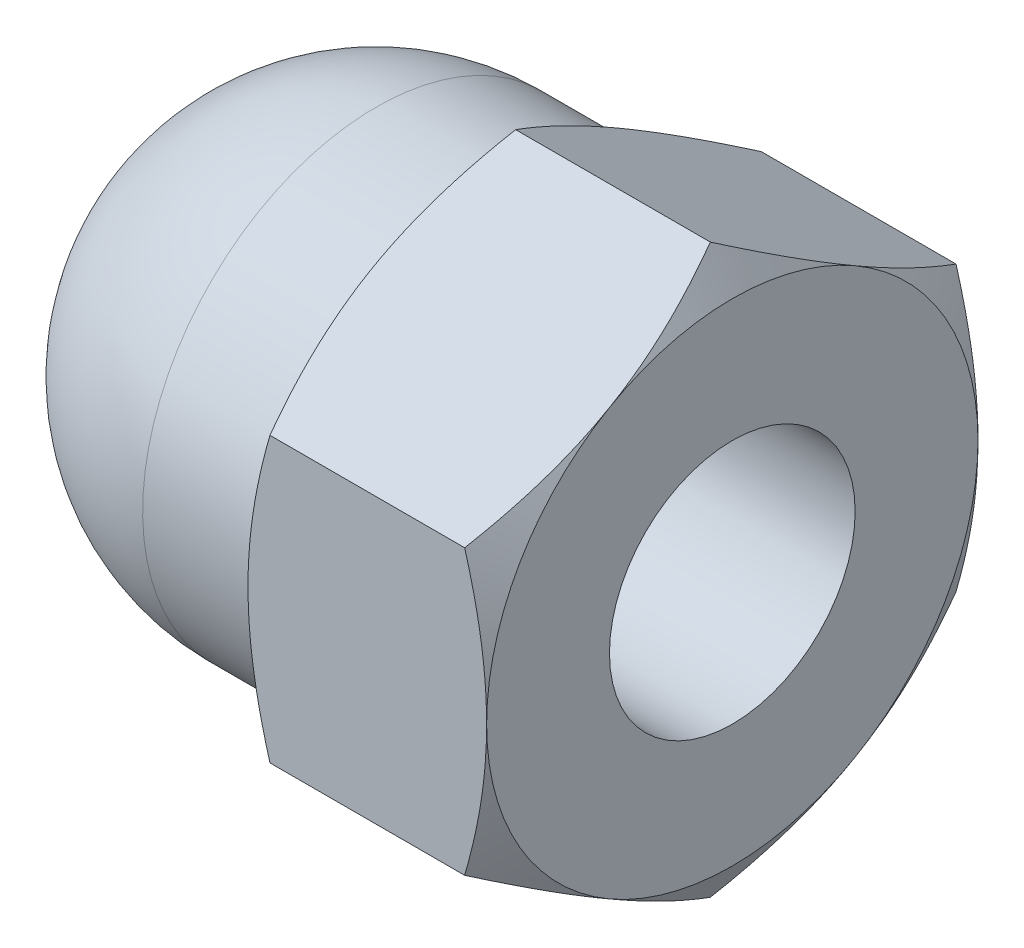
SolidWorks part; units mm, degrees
material "AISI 1020"
ref_plane "XY (Front)" through (0, 0, 0) normal (0, 0, 1) x (1, 0, 0)
ref_plane "XZ (Top)" through (0, 0, 0) normal (0, 1, 0) x (1, 0, 0)
ref_plane "YZ (Right)" through (0, 0, 0) normal (1, 0, 0) x (0, 0, -1)
ref_axis "X" through (-88.99, 0, 0) along (1, 0, 0)
ref_axis "Y" through (0, 55, 0) along (0, -1, 0)
ref_axis "Z" through (0, 0, -88.99) along (0, 0, 1)
sketch "Sketch1" plane through (0, 0, 0) normal (1, 0, 0) x (0, 0, -1)
  line L1 (0, 5.7735) -> (-5, 2.8868)
  line L2 (-5, 2.8868) -> (-5, -2.8868)
  line L3 (-5, -2.8868) -> (0, -5.7735)
  line L4 (0, -5.7735) -> (5, -2.8868)
  line L5 (5, -2.8868) -> (5, 2.8868)
  line L6 (5, 2.8868) -> (0, 5.7735)
  circle A0 centre (0, 0) radius 5 construction
  dimension "s" = 10
extrude "Boss-Extrude1" add sketch "Sketch1" against normal blind 12
sketch "Sketch2" plane through (0, 0, 0) normal (0, 0, 1) x (1, 0, 0)
  line L0 (-12, 0) -> (-10.1368, 0) construction
  line L2 (0, 5) -> (-0.4466, 5.7735)
  line L3 (0, 5.7735) -> (0, 2.8868) construction
  line L4 (-12, 5.7735) -> (0, 5.7735) construction
  line L5 (-0.4466, 5.7735) -> (0, 5.7735)
  line L6 (0, 5.7735) -> (0, 5)
  line L7 (-4.4091, 5.7735) -> (-13.8632, 5.7735)
  line L8 (-12, 0) -> (-13.8632, 0)
  line L9 (-4.4091, 5.7735) -> (-5, 4.75)
  line L10 (-5, 4.75) -> (-7.25, 4.75)
  line L11 (-2.4278, 5.7735) -> (-2.4278, 4.5313) construction
  line L13 (-10.1368, 0) -> (-8.6934, 2.5)
  line L14 (-8.6934, 2.5) -> (0, 2.5)
  line L15 (0, 2.8868) -> (0, -2.8868) construction
  line L16 (0, 2.5) -> (0, 0)
  line L17 (0, 0) -> (-10.1368, 0)
  line L18 (-8.6934, 2.5) -> (-9.625, 4.1136) construction
  line L19 (-12, 2.8868) -> (-12, -2.8868) construction
  line L20 (-13.8632, 0) -> (-13.8632, 5.7735)
  line L21 (-5, 4.75) -> (-5, 5.7735) construction
  arc A0 (-12, 0) -> (-7.25, 4.75) centre (-7.25, 0) cw
  dimension "D1" = 30
  dimension "dk" = 9.5
  dimension "m" = 5
  dimension "M_t" = 5
revolve "Cut-Revolve4" cut sketch "Sketch2" angle 360 about L0
cosmetic thread "Cosmetic Thread1" parameters "D2"=6
